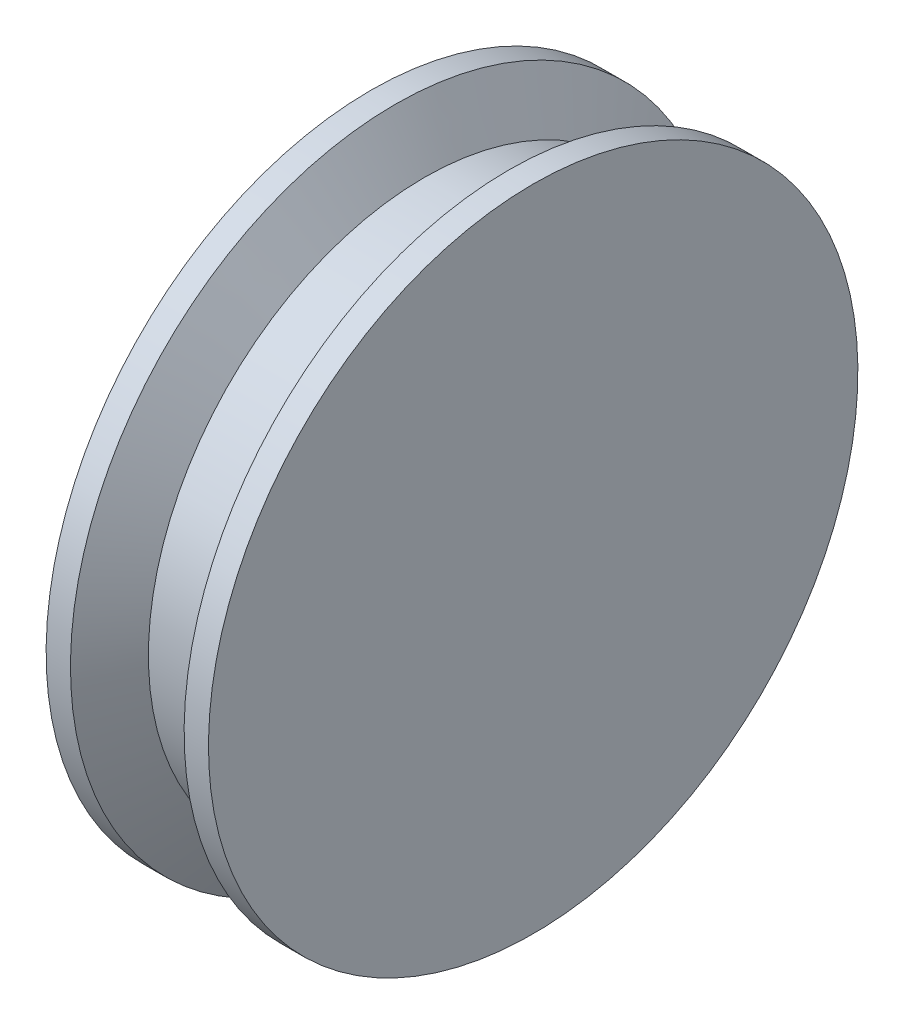
SolidWorks part; units mm, degrees
ref_plane "前视基准面" through (0, 0, 0) normal (0, 0, 1) x (1, 0, 0)
ref_plane "上视基准面" through (0, 0, 0) normal (0, 1, 0) x (1, 0, 0)
ref_plane "右视基准面" through (0, 0, 0) normal (1, 0, 0) x (0, 0, -1)
other "Configuration Table"
sketch "草图1" plane through (0, 0, 0) normal (0, 0, 1) x (1, 0, 0)
  line L0 (-131.3165, -36.0083) -> (-131.3165, 163.9917)
  line L1 (-131.3165, 163.9917) -> (-116.3165, 163.9917)
  line L2 (-116.3165, 163.9917) -> (-98.3165, 133.9917)
  line L3 (-98.3165, 133.9917) -> (-64.3165, 133.9917)
  line L4 (-64.3165, 133.9917) -> (-46.3165, 163.9917)
  line L5 (-46.3165, 163.9917) -> (-31.3165, 163.9917)
  line L6 (-31.3165, 163.9917) -> (-31.3165, -36.0083)
  line L7 (-31.3165, -36.0083) -> (-131.3165, -36.0083)
  dimension "D1" = 200
  dimension "D2" = 200
  dimension "D3" = 100
  dimension "D4" = 15
  dimension "D5" = 15
  dimension "D6" = 34
  dimension "D7" = 30
  dimension "D8" = 18
revolve "旋转1" add sketch "草图1" angle 360 about L7
sketch "草图4" plane through (-131.3165, 0, 0) normal (-1, 0, 0) x (0, 0, 1)
  circle A0 centre (0, -36.0083) radius 10
  dimension "D1" = 20
extrude "切除-拉伸1" cut sketch "草图4" against normal blind 40
sketch "草图5" plane through (-131.3165, 0, 0) normal (-1, 0, 0) x (0, 0, 1)
  line L0 (0, -36.0083) -> (0, -92.0314)
sketch "草图6" plane through (-31.3165, 0, 0) normal (1, 0, 0) x (0, 0, -1)
  line L0 (0, -36.0083) -> (0, -92.0314)
ref_plane "基准面1" through (0, 0, 0) normal (0, 0, 1) x (1, 0, 0)
sketch "草图9" plane through (0, 0, 0) normal (0, 0, 1) x (1, 0, 0)
  line L0 (-121.3165, -31.0083) -> (-121.3165, -41.0083)
  line L1 (-121.3165, -41.0083) -> (-101.3165, -41.0083)
  line L2 (-101.3165, -41.0083) -> (-101.3165, -31.0083)
  line L3 (-101.3165, -31.0083) -> (-121.3165, -31.0083)
  line L4 (-131.3165, -36.0083) -> (-131.3165, -92.0314) construction
  line L5 (-131.3165, -31.0083) -> (-121.3165, -31.0083)
  line L6 (-131.3165, 163.9917) -> (-131.3165, -236.0083) construction
  line L7 (-121.3165, -41.0083) -> (-131.3165, -41.0083)
  line L8 (-131.3165, -41.0083) -> (-131.3165, -31.0083)
  circle A0 centre (-101.3165, -36.0083) radius 5
  circle A1 centre (-121.3165, -36.0083) radius 5
  point P6 (-121.3165, -36.0083)
  dimension "D1" = 20
  dimension "D2" = 10
  dimension "D3" = 10
  dimension "D4" = 200
extrude "切除-拉伸5" cut sketch "草图9" against normal blind 14 contours A1 L1 A0 L3 | L2 A0 | L2 A0 | L0 A1 | L0 A1 region at (-119.1944, -36.0083, 0) region at (-111.3165, -36.0083, 0) region at (-123.4386, -36.0083, 0) region at (-99.1944, -36.0083, 0) region at (-103.4386, -36.0083, 0)
extrude "切除-拉伸6" cut sketch "草图9<4>" against normal blind 14 contours A1 L5 L8 L7 region at (-128.1775, -36.0083, 0)
sketch "草图9<4>" plane through (0, 0, 0) normal (0, 0, 1) x (1, 0, 0) same geometry as "草图9"
